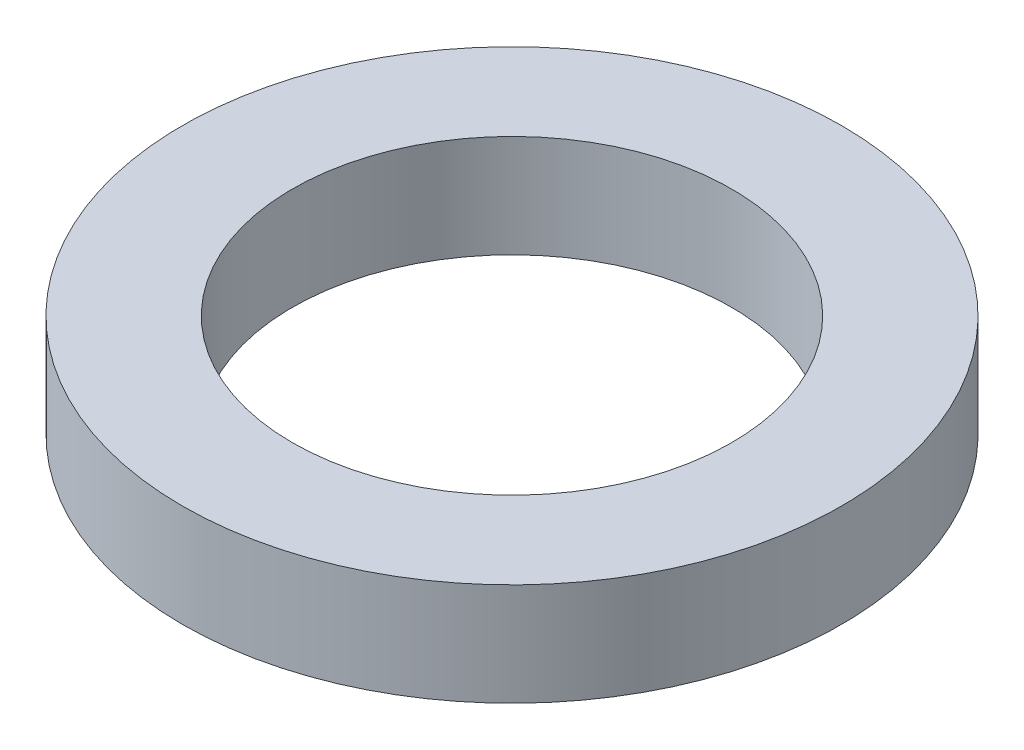
SolidWorks part; units mm, degrees
ref_plane "Front Plane" through (0, 0, 0) normal (0, 0, 1) x (1, 0, 0)
ref_plane "Top Plane" through (0, 0, 0) normal (0, 1, 0) x (1, 0, 0)
ref_plane "Right Plane" through (0, 0, 0) normal (1, 0, 0) x (0, 0, -1)
sketch "Sketch1" plane through (0, 0, 0) normal (0, 1, 0) x (1, 0, 0)
  circle A0 centre (0, 0) radius 22.5
  dimension "FLANGE_OD" = 45
extrude "Boss-Extrude1" add sketch "Sketch1" along normal blind 7
sketch "Sketch2" plane through (0, 0, 0) normal (0, 1, 0) x (1, 0, 0)
  circle A0 centre (0, 0) radius 15
  dimension "BORE_D" = 30
extrude "Cut-Extrude1" cut sketch "Sketch2" along normal through all
sketch "Sketch3" plane through (0, 7, 0) normal (0, 1, 0) x (1, 0, 0)
  circle A0 centre (0, 0) radius 8.8076 construction
  circle A1 centre (-8.8076, 0) radius 1.5
  dimension "BOLT_D" = 3
  dimension "BOLT_PCD" = 17.6152
extrude "Cut-Extrude2" cut sketch "Sketch3" against normal blind 6.871 rebuild error yes
pattern_circular "CirPattern1" count 4 over 360 rebuild error yes
